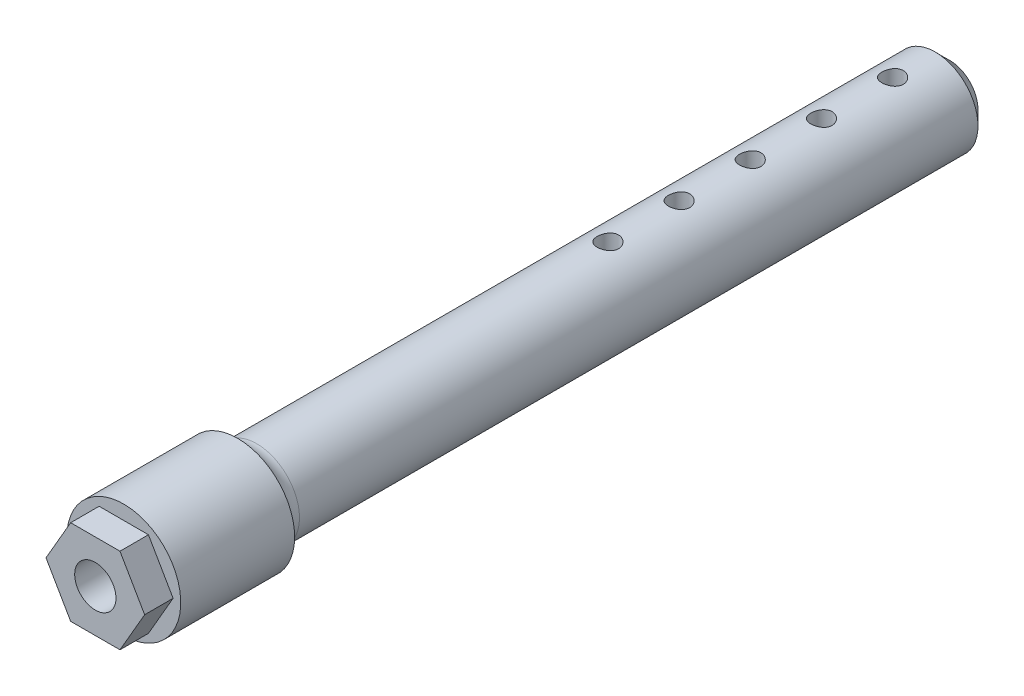
SolidWorks part; units mm, degrees
ref_plane "Front Plane" through (0, 0, 0) normal (0, 0, 1) x (1, 0, 0)
ref_plane "Top Plane" through (0, 0, 0) normal (0, 1, 0) x (1, 0, 0)
ref_plane "Right Plane" through (0, 0, 0) normal (1, 0, 0) x (0, 0, -1)
sketch "Sketch1" plane through (0, 0, 0) normal (0, 0, 1) x (1, 0, 0)
  line L1 (-3.4641, 0) -> (-1.7321, -3)
  line L2 (-1.7321, -3) -> (1.7321, -3)
  line L3 (1.7321, -3) -> (3.4641, 0)
  line L4 (3.4641, 0) -> (1.7321, 3)
  line L5 (1.7321, 3) -> (-1.7321, 3)
  line L6 (-1.7321, 3) -> (-3.4641, 0)
  circle A0 centre (0, 0) radius 3 construction
  circle A1 centre (0, 0) radius 1.45
  dimension "D2" = 2.9
  dimension "D1" = 6
extrude "Boss-Extrude1" add sketch "Sketch1" along normal blind 2
sketch "Sketch2" plane through (0, 0, 0) normal (0, 0, -1) x (-1, 0, 0)
  circle A0 centre (0, 0) radius 4
  circle A1 centre (0, 0) radius 1.45
  dimension "D1" = 8
extrude "Boss-Extrude2" add sketch "Sketch2" along normal blind 8
sketch "Sketch3" plane through (0, 0, -8) normal (0, 0, -1) x (-1, 0, 0)
  circle A0 centre (0, 0) radius 3
  dimension "D1" = 6
extrude "Boss-Extrude3" add sketch "Sketch3" along normal blind 50
fillet "Fillet1" radius 1.4 2 edges at (-1.45, 0, -8) (-3, 0, -8)
chamfer "Chamfer1" distance 1 angle 45 1 edges at (-3, 0, -58)
sketch "Sketch4" plane through (0, 0, 0) normal (0, 1, 0) x (1, 0, 0)
  line L0 (0, 47.5755) -> (0, 58.8414) construction
  line L1 (-3, 57) -> (3, 57) construction
  circle A0 centre (0, 54) radius 0.75
  circle A1 centre (0, 49) radius 0.75
  circle A2 centre (0, 44) radius 0.75
  circle A3 centre (0, 39) radius 0.75
  circle A4 centre (0, 34) radius 0.75
  dimension "D1" = 1.5
  dimension "D2" = 3
  dimension "D3" = 5
extrude "Cut-Extrude1" cut sketch "Sketch4" against normal through all both and the other way through all
